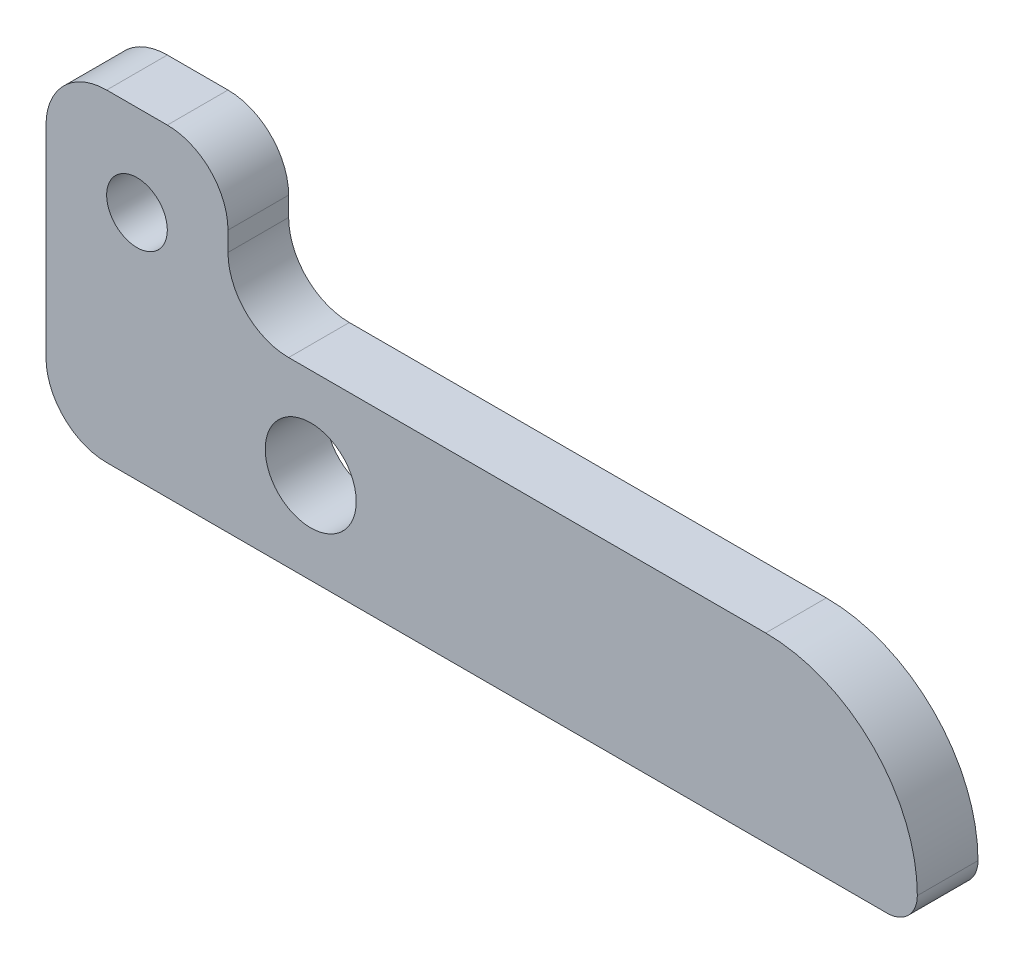
SolidWorks part; units mm, degrees
ref_plane "Front" through (0, 0, 0) normal (0, 0, 1) x (1, 0, 0)
ref_plane "Top" through (0, 0, 0) normal (0, 1, 0) x (1, 0, 0)
ref_plane "Right" through (0, 0, 0) normal (1, 0, 0) x (0, 0, -1)
sketch "Sketch1" plane through (0, 0, 0) normal (0, 0, 1) x (1, 0, 0)
  line L0 (-2.1678, 169.7123) -> (-2.1678, 174.3504)
  line L1 (0.5965, 163.7123) -> (20.5598, 163.7123)
  line L2 (20.5598, 163.7123) -> (20.5598, 169.7123)
  line L3 (20.5598, 169.7123) -> (-2.1678, 169.7123)
  line L5 (0.5598, 166.7123) -> (-5.1678, 171.3504) construction
  line L6 (-2.9035, 166.7123) -> (20.5598, 166.7123) construction
  line L7 (0.5598, 166.7123) -> (-0.9402, 166.7123) construction
  line L12 (-2.1678, 174.3504) -> (-8.1678, 174.3504)
  line L13 (-8.1678, 174.3504) -> (-8.1678, 163.7123)
  line L14 (-8.1678, 163.7123) -> (0.5965, 163.7123)
  circle A0 centre (0.5598, 166.7123) radius 1.5
  circle A1 centre (-5.1678, 171.3504) radius 1
  dimension "D4" = 141
  dimension "D5" = 3
  dimension "D6" = 2
  dimension "D8" = 2
  dimension "D9" = 2
  dimension "D1" = 7.37
  dimension "D7" = 2
  dimension "D2" = 20
  dimension "D3" = 6
extrude "Boss-Extrude1" add sketch "Sketch1" along normal blind 2
fillet "Fillet7" radius 5 1 edges at (20.5598, 169.7123, 1)
fillet "Fillet8" radius 1 1 edges at (20.5598, 163.7123, 1)
fillet "Fillet9" radius 2 4 edges at (-2.1678, 169.7123, 1) (-2.1678, 174.3504, 1) (-8.1678, 174.3504, 1) (-8.1678, 163.7123, 1)
